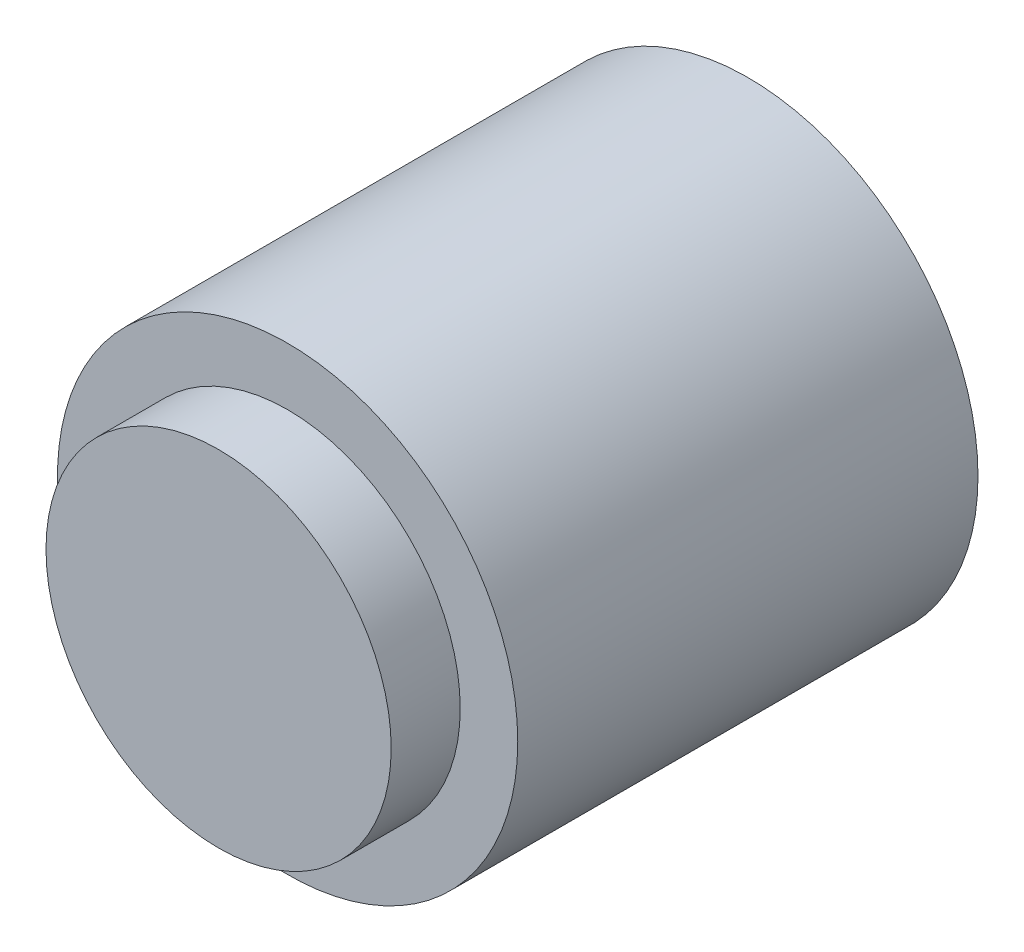
SolidWorks part; units mm, degrees
material "POM Acetal Copolymer"
ref_plane "Front Plane" through (0, 0, 0) normal (0, 0, 1) x (1, 0, 0)
ref_plane "Top Plane" through (0, 0, 0) normal (0, 1, 0) x (1, 0, 0)
ref_plane "Right Plane" through (0, 0, 0) normal (1, 0, 0) x (0, 0, -1)
sketch "Extrude sketch 1" plane through (0, 0, 0) normal (0, 0, 1) x (1, 0, 0)
  circle A0 centre (118, 0) radius 20
  dimension "D1" = 40
extrude "Extrude 1" add sketch "Extrude sketch 1" along normal blind 40 from offset 592 separate body
sketch "Extrude sketch 2" plane through (0, 0, 0) normal (0, 0, 1) x (1, 0, 0)
  circle A0 centre (118, 0) radius 15
  dimension "D1" = 30
extrude "Extrude 2" add sketch "Extrude sketch 2" along normal blind 6 from offset 632 separate body
combine bodies "Combine (weld / assembly of features)" operation type add bodies to combine 102 101
